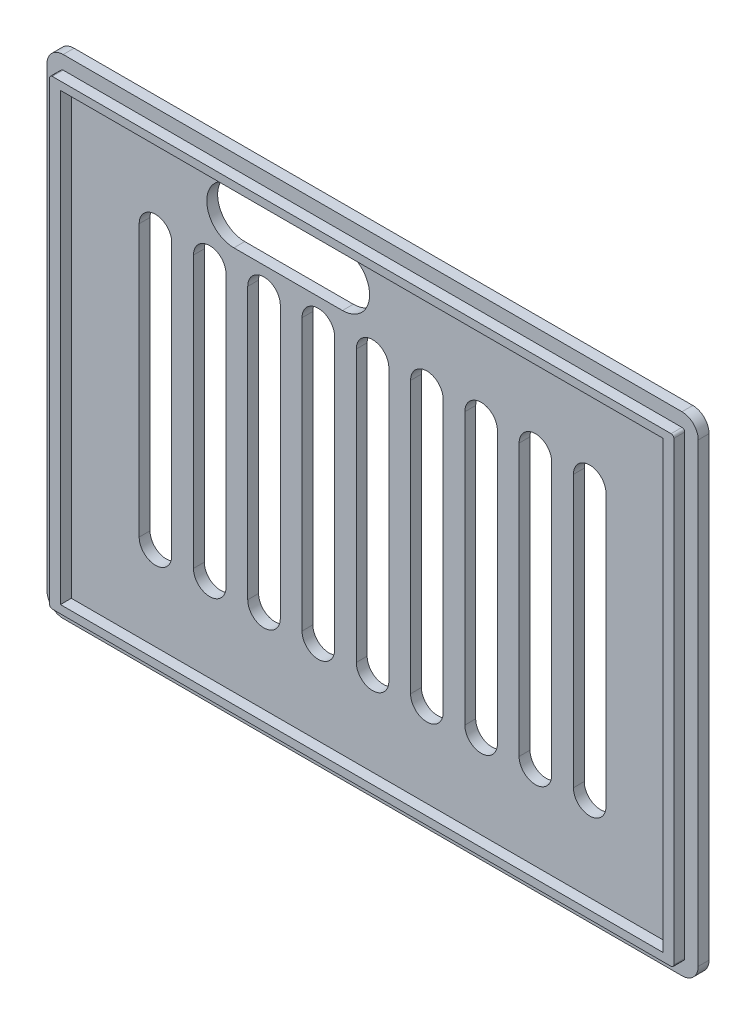
SolidWorks part; units mm, degrees
ref_plane "Plan de face" through (0, 0, 0) normal (0, 0, 1) x (1, 0, 0)
ref_plane "Plan de dessus" through (0, 0, 0) normal (0, 1, 0) x (1, 0, 0)
ref_plane "Plan de droite" through (0, 0, 0) normal (1, 0, 0) x (0, 0, -1)
sketch "Esquisse1" plane through (0, 0, 0) normal (0, 0, 1) x (1, 0, 0)
  line L1 (60, -45) -> (-60, -45)
  line L2 (60, -45) -> (60, 45)
  line L3 (60, 45) -> (-60, 45)
  line L4 (-60, -45) -> (-60, 45)
  line L5 (60, -45) -> (-60, 45) construction
  line L6 (60, 45) -> (-60, -45) construction
  point P0 (0, 0)
  dimension "D1" = 120
  dimension "D2" = 90
extrude "Boss.-Extru.1" add sketch "Esquisse1" along normal blind 2
sketch "Esquisse2" plane through (0, 0, 2) normal (0, 0, 1) x (1, 0, 0)
  line L1 (57.5, -42.5) -> (-57.5, -42.5)
  line L2 (57.5, -42.5) -> (57.5, 42.5)
  line L3 (57.5, 42.5) -> (-57.5, 42.5)
  line L4 (-57.5, -42.5) -> (-57.5, 42.5)
  line L5 (57.5, -42.5) -> (-57.5, 42.5) construction
  line L6 (57.5, 42.5) -> (-57.5, -42.5) construction
  line L7 (55.5, -41.0217) -> (-55.5, -41.0217)
  line L8 (55.5, -41.0217) -> (55.5, 41.0217)
  line L9 (55.5, 41.0217) -> (-55.5, 41.0217)
  line L10 (-55.5, -41.0217) -> (-55.5, 41.0217)
  line L11 (55.5, -41.0217) -> (-55.5, 41.0217) construction
  line L12 (55.5, 41.0217) -> (-55.5, -41.0217) construction
  point P0 (0, 0)
  point P6 (0, 0)
  dimension "D1" = 115
  dimension "D2" = 85
  dimension "D3" = 2
extrude "Boss.-Extru.2" add sketch "Esquisse2" along normal blind 2
sketch "Esquisse3" plane through (0, 0, 0) normal (0, 0, -1) x (-1, 0, 0)
  line L0 (5.5484, 34.875) -> (25.5484, 34.875) construction
  line L1 (5.5484, 39.875) -> (25.5484, 39.875)
  line L2 (5.5484, 29.875) -> (25.5484, 29.875)
  arc A0 (5.5484, 39.875) -> (5.5484, 29.875) centre (5.5484, 34.875) ccw
  arc A1 (25.5484, 29.875) -> (25.5484, 39.875) centre (25.5484, 34.875) ccw
  point P2 (15.5484, 34.875)
  dimension "D1" = 20
  dimension "D2" = 10
extrude "Enlèv. mat.-Extru.1" cut sketch "Esquisse3" against normal blind 2
fillet "Congé1" radius 3 4 edges at (60, 45, 1) (-60, -45, 1) (-60, 45, 1) (60, -45, 1)
fillet "Congé2" radius 0.5 4 edges at (57.5, -42.5, 3) (57.5, 42.5, 3) (-57.5, 42.5, 3) (-57.5, -42.5, 3)
sketch "Esquisse4" plane through (0, 0, 0) normal (0, 0, -1) x (-1, 0, 0)
  line L0 (0, 25) -> (0, -25) construction
  line L1 (3, 25) -> (3, -25)
  line L2 (-3, 25) -> (-3, -25)
  arc A0 (3, 25) -> (-3, 25) centre (0, 25) ccw
  arc A1 (-3, -25) -> (3, -25) centre (0, -25) ccw
  point P3 (0, 0)
  dimension "D3" = 0
  dimension "D1" = 50
  dimension "D2" = 6
extrude "Enlèv. mat.-Extru.2" cut sketch "Esquisse4" against normal through all
pattern_linear "Répétition linéaire1" count 5 spacing 10 along (-1, 0, 0) count 5 spacing 10 along (1, 0, 0) of "Enlèv. mat.-Extru.2"
